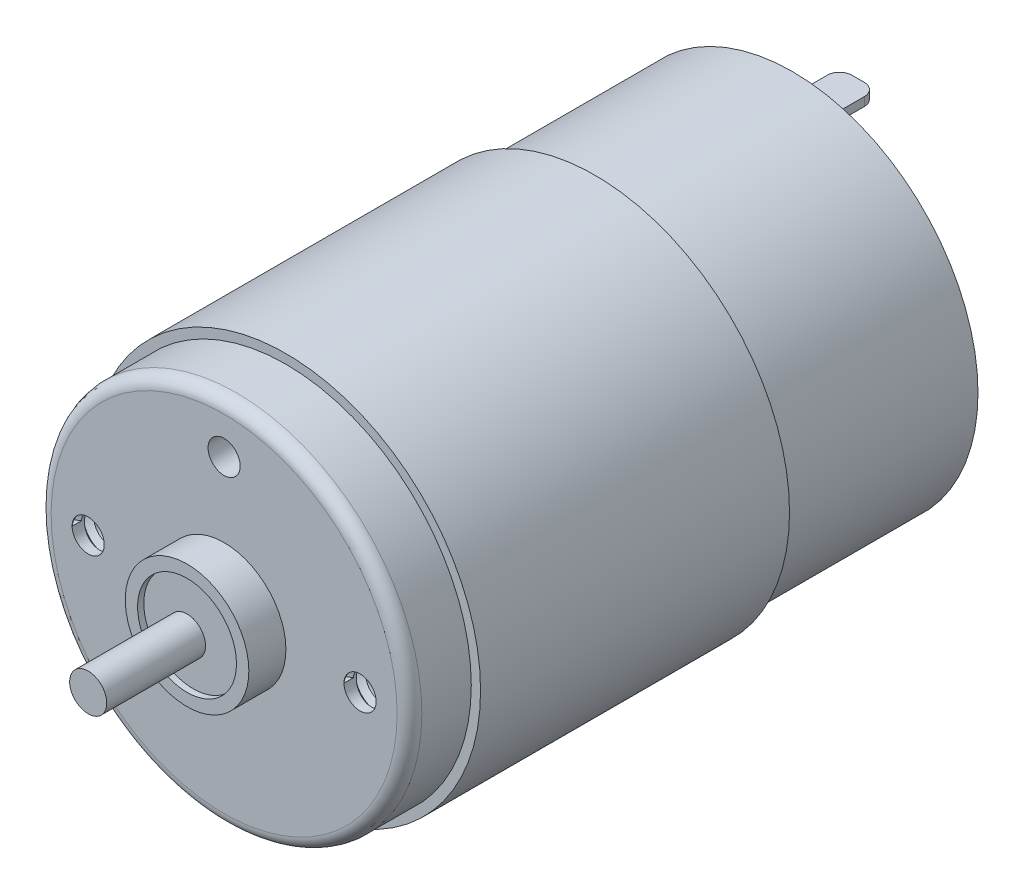
SolidWorks part; units mm, degrees
ref_plane "Alzado" through (0, 0, 0) normal (0, 0, 1) x (1, 0, 0)
ref_plane "Planta" through (0, 0, 0) normal (0, 1, 0) x (1, 0, 0)
ref_plane "Vista lateral" through (0, 0, 0) normal (1, 0, 0) x (0, 0, -1)
sketch "Croquis1" plane through (0, 0, 0) normal (0, 0, 1) x (1, 0, 0)
  circle A0 centre (0, 0) radius 15
  dimension "D1" = 30
extrude "Saliente-Extruir1" add sketch "Croquis1" along normal blind 46
sketch "Croquis2" plane through (0, 0, 0) normal (0, 0, -1) x (-1, 0, 0)
  circle A0 centre (0, 0) radius 15.75
  dimension "D1" = 31.5
extrude "Saliente-Extruir2" add sketch "Croquis2" against normal blind 41
sketch "Croquis3" plane through (0, 0, 0) normal (0, 0, -1) x (-1, 0, 0)
  circle A0 centre (0, 0) radius 15.75
extrude "Cortar-Extruir1" cut sketch "Croquis3" against normal blind 16
sketch "Croquis4" plane through (0, 0, 16) normal (0, 0, -1) x (-1, 0, 0)
  circle A1 centre (0, 0) radius 15
  dimension "D1" = 30
extrude "Saliente-Extruir3" add sketch "Croquis4" along normal blind 16
sketch "Croquis5" plane through (0, 0, 46) normal (0, 0, 1) x (1, 0, 0)
  line L0 (0, 0) -> (-11, 0)
  line L1 (-11, 0) -> (11, 0)
  circle A0 centre (-11, 0) radius 1.3
  circle A1 centre (11, 0) radius 1.3
  dimension "D3" = 2.6
  dimension "D4" = 2.6
  dimension "D1" = 11
  dimension "D2" = 22
extrude "Cortar-Extruir2" cut sketch "Croquis5" against normal blind 7 contours A0 | A1 region at (-12.2632, 0, 46) region at (11, 1.2632, 46)
thread "Rosca1" pitch 1 method cut profile "Perfil de rosca2" start angle 0, offset 0, length 3, pitch 1, diameter 2.6
ref_plane "Plano2" through (9.7, 0, 46) normal (0, -1, 0) x (-1, 0, 0)
sketch "Perfil de rosca2" plane through (9.7, 0, 46) normal (0, -1, 0) x (-1, 0, 0)
  line L0 (0, 0) -> (0, 1) construction
  line L1 (0, 0) -> (0.5413, 0.3125)
  line L2 (0.5413, 0.3125) -> (0.5413, 0.4375)
  line L3 (0.5413, 0.4375) -> (0, 0.75)
  line L4 (0.5413, 0.375) -> (0, 0.375) construction
  line L11 (0, 0) -> (0, 0.75)
  point P2 (0, 0)
  dimension "Pitch" = 1
  dimension "Profile_Angle" = 60
  dimension "Profile_Land" = 0.125
  dimension "Profile_Height" = 0.5413
thread "Rosca2" pitch 1 method cut profile "Perfil de rosca3" start angle 0, offset 0, length 3, pitch 1, diameter 2.6
ref_plane "Plano3" through (-12.3, 0, 46) normal (0, -1, 0) x (-1, 0, 0)
sketch "Perfil de rosca3" plane through (-12.3, 0, 46) normal (0, -1, 0) x (-1, 0, 0)
  line L0 (0, 0) -> (0, 1) construction
  line L1 (0, 0) -> (0.5413, 0.3125)
  line L2 (0.5413, 0.3125) -> (0.5413, 0.4375)
  line L3 (0.5413, 0.4375) -> (0, 0.75)
  line L4 (0.5413, 0.375) -> (0, 0.375) construction
  line L11 (0, 0) -> (0, 0.75)
  point P2 (0, 0)
  dimension "Pitch" = 1
  dimension "Profile_Angle" = 60
  dimension "Profile_Land" = 0.125
  dimension "Profile_Height" = 0.5413
sketch "Croquis15" plane through (0, 0, 46) normal (0, 0, 1) x (1, 0, 0)
  circle A0 centre (0, 0) radius 1.5
  circle A1 centre (0, 0) radius 5
  dimension "D1" = 3
  dimension "D2" = 10
extrude "Saliente-Extruir4" add sketch "Croquis15" along normal blind 3
sketch "Croquis17" plane through (0, 0, 46) normal (0, 0, 1) x (1, 0, 0)
  circle A0 centre (0, 0) radius 1.5
extrude "Saliente-Extruir5" add sketch "Croquis17" along normal blind 11
sketch "Croquis19" plane through (0, 0, 49) normal (0, 0, 1) x (1, 0, 0)
  circle A0 centre (0, 0) radius 4
  dimension "D1" = 8
extrude "Cortar-Extruir3" cut sketch "Croquis19" against normal blind 0.5
fillet "Redondeo2" radius 1 1 edges at (15, 0, 46)
sketch "Croquis20" plane through (0, 0, 46) normal (0, 0, 1) x (1, 0, 0)
  line L0 (0, 0) -> (0, 11)
  circle A0 centre (0, 11) radius 1.3
  dimension "D2" = 2.6
  dimension "D1" = 11
extrude "Cortar-Extruir4" cut sketch "Croquis20" against normal blind 3 contours A0 region at (0.8932, 10.1068, 46)
sketch "Croquis21" plane through (0, 0, 0) normal (0, 0, -1) x (-1, 0, 0)
  circle A0 centre (0, 0) radius 5
  dimension "D1" = 10
extrude "Saliente-Extruir6" add sketch "Croquis21" along normal blind 3
sketch "Croquis22" plane through (0, 0, -3) normal (0, 0, -1) x (-1, 0, 0)
  circle A0 centre (0, 0) radius 4
  dimension "D1" = 8
extrude "Cortar-Extruir5" cut sketch "Croquis22" against normal blind 0.5
sketch "Croquis23" plane through (0, 0, -2.5) normal (0, 0, -1) x (-1, 0, 0)
  circle A0 centre (0, 0) radius 1.5
  dimension "D1" = 3
extrude "Saliente-Extruir7" add sketch "Croquis23" along normal blind 6.7
sketch "Croquis24" plane through (0, 0, 0) normal (0, 0, -1) x (-1, 0, 0)
  line L0 (0, 0) -> (0, 11.5)
  line L2 (1.5, 11.85) -> (-1.5, 11.85)
  line L3 (1.5, 11.85) -> (1.5, 11.15)
  line L4 (1.5, 11.15) -> (-1.5, 11.15)
  line L5 (-1.5, 11.85) -> (-1.5, 11.15)
  line L6 (1.5, 11.85) -> (-1.5, 11.15) construction
  line L7 (1.5, 11.15) -> (-1.5, 11.85) construction
  dimension "D1" = 11.5
  dimension "D2" = 0.7
  dimension "D3" = 3
extrude "Saliente-Extruir8" add sketch "Croquis24" along normal blind 5.3 contours L2 L5 L4 L3 region at (-1.4692, 11.5, 0)
sketch "Croquis25" plane through (0, 0, 0) normal (0, 0, -1) x (-1, 0, 0)
  line L0 (0, 0) -> (0, -11.5)
  line L2 (1.5, -11.15) -> (-1.5, -11.15)
  line L3 (1.5, -11.15) -> (1.5, -11.85)
  line L4 (1.5, -11.85) -> (-1.5, -11.85)
  line L5 (-1.5, -11.15) -> (-1.5, -11.85)
  line L6 (1.5, -11.15) -> (-1.5, -11.85) construction
  line L7 (1.5, -11.85) -> (-1.5, -11.15) construction
  dimension "D1" = 11.5
  dimension "D2" = 0.7
  dimension "D3" = 3
extrude "Saliente-Extruir9" add sketch "Croquis25" along normal blind 5.3 contours L2 L5 L4 L3 region at (-1.4692, -11.5, 0)
fillet "Redondeo5" radius 1 4 edges at (1.5, 11.5, -5.3) (-1.5, 11.5, -5.3) (1.5, -11.5, -5.3) (-1.5, -11.5, -5.3)
